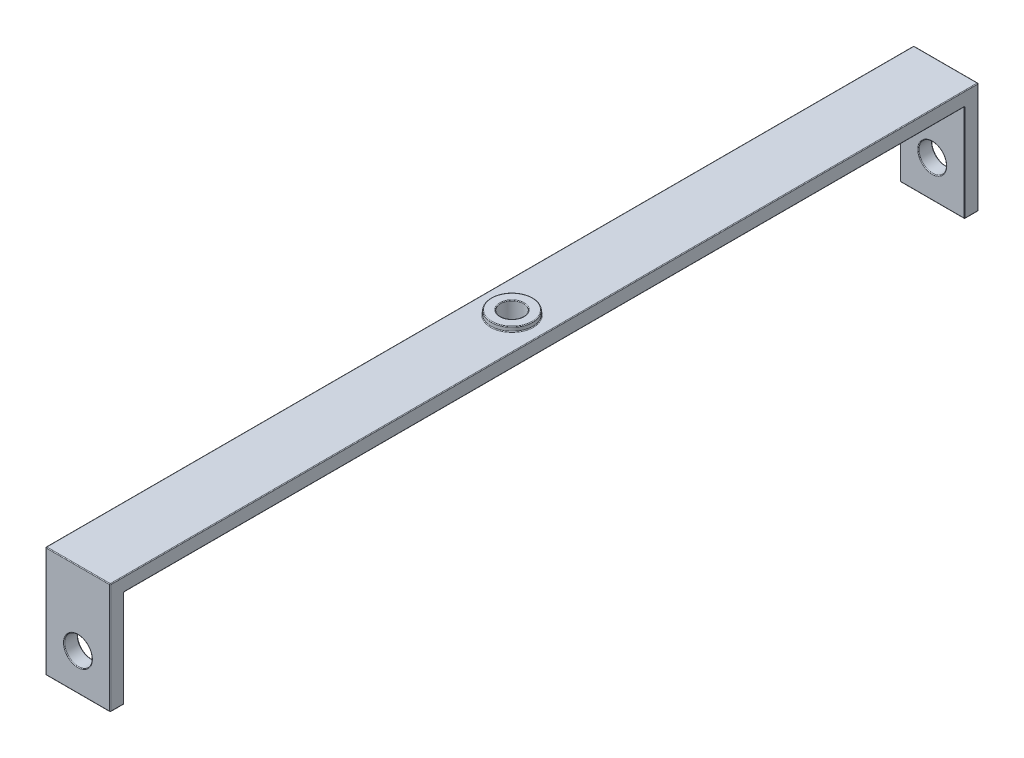
SolidWorks part; units mm, degrees
ref_plane "Front Plane" through (0, 0, 0) normal (0, 0, 1) x (1, 0, 0)
ref_plane "Top Plane" through (0, 0, 0) normal (0, 1, 0) x (1, 0, 0)
ref_plane "Right Plane" through (0, 0, 0) normal (1, 0, 0) x (0, 0, -1)
sketch "Sketch1" plane through (0, 0, 0) normal (1, 0, 0) x (0, 0, -1)
  line L0 (-47, -12) -> (-47, 0)
  line L1 (-47, 0) -> (47, 0)
  line L2 (47, 0) -> (47, -12)
  line L3 (-45.5, -12) -> (-45.5, -1.5)
  line L4 (-45.5, -1.5) -> (45.5, -1.5)
  line L5 (45.5, -1.5) -> (45.5, -12)
  line L6 (-47, -12) -> (-45.5, -12)
  line L7 (45.5, -12) -> (47, -12)
  point P5 (0, 0)
  dimension "D1" = 94
  dimension "D2" = 12
  dimension "D3" = 1.5
extrude "Boss-Extrude1" add sketch "Sketch1" along normal blind 3.5 and the other way blind 3.5
sketch "Sketch2" plane through (0, 0, 0) normal (0, 1, 0) x (1, 0, 0)
  circle A0 centre (0, 0) radius 1.25
  dimension "D1" = 2.5
extrude "Cut-Extrude1" cut sketch "Sketch2" against normal up to surface (1.5 mm away) up to face at (0, -1.5, 0)
sketch "Sketch3" plane through (0, 0, 0) normal (0, 1, 0) x (1, 0, 0)
  circle A0 centre (0, 0) radius 1.25 construction
  circle A1 centre (0, 0) radius 1.25
  circle A2 centre (0, 0) radius 2.25
  dimension "D1" = 1
extrude "Boss-Extrude3" add sketch "Sketch3" along normal blind 0.5
sketch "Sketch5" plane through (0, 0, 0) normal (0, 0, 1) x (1, 0, 0)
  line L0 (0, 0.5) -> (0, -8) construction
  line L1 (2.25, 0.5) -> (-2.25, 0.5) construction
  circle A0 centre (0, -8) radius 1.5
  dimension "D2" = 3
  dimension "D1" = 8.5
extrude "Cut-Extrude5" cut sketch "Sketch5" against normal through all both and the other way through all
fillet "Fillet1" radius 0.075 32 edges at (1.5, -8, 47) (1.5, -8, -47) (-1.5, -8, 45.5) (1.5, -8, -45.5) (0, 0.5, 1.25) (0, 0, 2.25) (0, 0.5, 2.25) (0, -1.5, -1.25) (3.5, -12, 46.25) (3.5, -6.75, 45.5) (3.5, -1.5, 0) (3.5, -6.75, -45.5) (3.5, -12, -46.25) (3.5, -6, -47) (3.5, 0, 0) (-3.5, -12, 46.25) (-3.5, -6.75, 45.5) (-3.5, -1.5, 0) (-3.5, -6.75, -45.5) (-3.5, -12, -46.25) (-3.5, -6, -47) (-3.5, 0, 0) (-3.5, -6, 47) (0, -12, 45.5) (0, -1.5, 45.5) (0, -1.5, -45.5) (0, -12, -45.5) (0, -12, -47) (0, 0, -47) (0, 0, 47) (0, -12, 47) (3.5, -6, 47)
